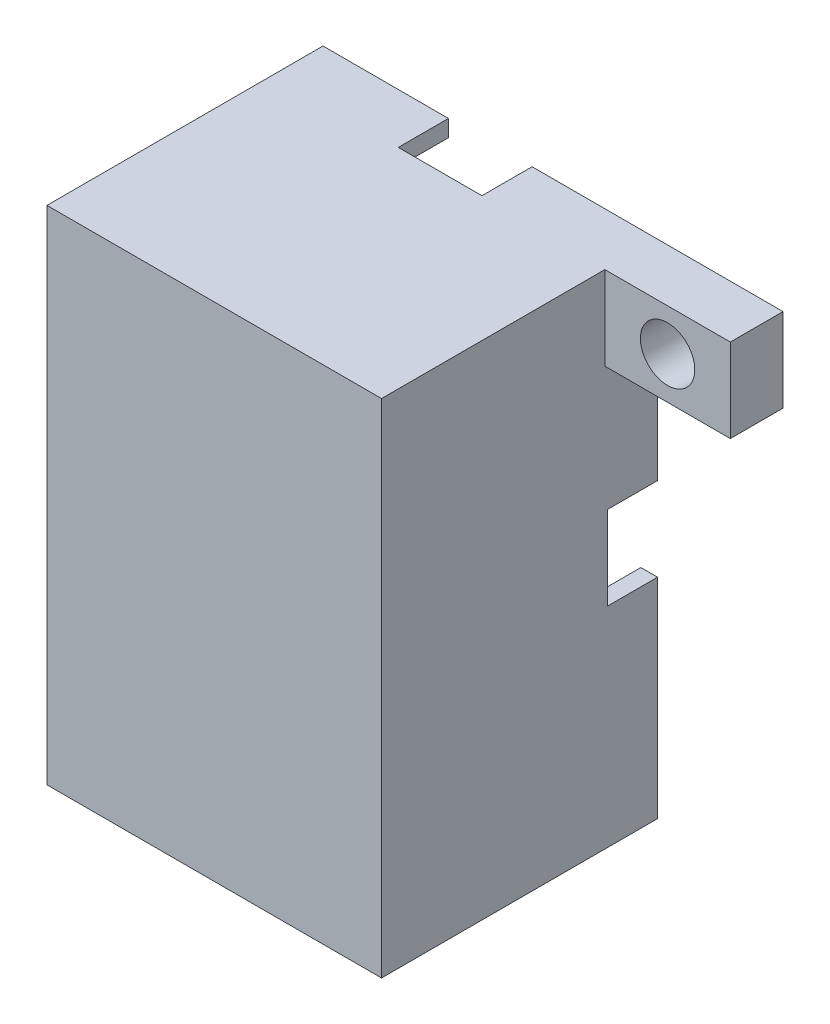
SolidWorks part; units mm, degrees
ref_plane "Front Plane" through (0, 0, 0) normal (0, 0, 1) x (1, 0, 0)
ref_plane "Top Plane" through (0, 0, 0) normal (0, 1, 0) x (1, 0, 0)
ref_plane "Right Plane" through (0, 0, 0) normal (1, 0, 0) x (0, 0, -1)
sketch "Sketch1" plane through (0, 0, 0) normal (0, 0, 1) x (1, 0, 0)
  line L1 (0, 0) -> (20, 0)
  line L2 (0, 0) -> (0, 30)
  line L3 (0, 30) -> (20, 30)
  line L4 (20, 0) -> (20, 30)
  line L5 (1, 1) -> (19, 1)
  line L6 (1, 1) -> (1, 29)
  line L7 (1, 29) -> (19, 29)
  line L8 (19, 1) -> (19, 29)
  dimension "D1" = 1
  dimension "D2" = 1
  dimension "D3" = 1
  dimension "D4" = 1
  dimension "D5" = 20
  dimension "D6" = 30
extrude "Boss-Extrude1" add sketch "Sketch1" along normal blind 15
sketch "Sketch2" plane through (0, 0, 15) normal (0, 0, 1) x (1, 0, 0)
  line L1 (0, 30) -> (20, 30)
  line L2 (0, 30) -> (0, 0)
  line L3 (0, 0) -> (20, 0)
  line L4 (20, 30) -> (20, 0)
extrude "Boss-Extrude2" add sketch "Sketch2" along normal blind 1.5
sketch "Sketch3" plane through (0, 0, 0) normal (0, 0, -1) x (-1, 0, 0)
  line L1 (-20, 30) -> (-27.5, 30)
  line L2 (-20, 30) -> (-20, 25)
  line L3 (-20, 25) -> (-27.5, 25)
  line L4 (-27.5, 30) -> (-27.5, 25)
  circle A0 centre (-23.75, 27.5) radius 1.625
  point P7 (-23.75, 30)
  point P8 (-12.5, 10.9347)
  point P9 (-27.5, 27.5)
  dimension "D3" = 3.25
  dimension "D1" = 7.5
  dimension "D2" = 5
extrude "Boss-Extrude3" add sketch "Sketch3" against normal blind 3.15
sketch "Sketch4" plane through (0, 0, 0) normal (-1, 0, 0) x (0, 0, 1)
  line L0 (0, 30) -> (0, 0) construction
  line L1 (0, 17.5) -> (3, 17.5)
  line L2 (0, 17.5) -> (0, 12.5)
  line L3 (0, 12.5) -> (3, 12.5)
  line L4 (3, 17.5) -> (3, 12.5)
  point P6 (0, 15)
  point P7 (0, 15)
  dimension "D1" = 3
  dimension "D2" = 0
  dimension "D3" = 5
extrude "Cut-Extrude1" cut sketch "Sketch4" against normal through all both and the other way through all
sketch "Sketch5" plane through (0, 0, 0) normal (0, -1, 0) x (1, 0, 0)
  line L0 (0, 0) -> (20, 0) construction
  line L1 (7.5, 0) -> (12.5, 0)
  line L2 (7.5, 0) -> (7.5, 3)
  line L3 (7.5, 3) -> (12.5, 3)
  line L4 (12.5, 0) -> (12.5, 3)
  point P6 (10, 0)
  point P7 (10, 0)
  dimension "D1" = 5
  dimension "D2" = 3
  dimension "D3" = 0
extrude "Cut-Extrude2" cut sketch "Sketch5" against normal through all both and the other way through all
